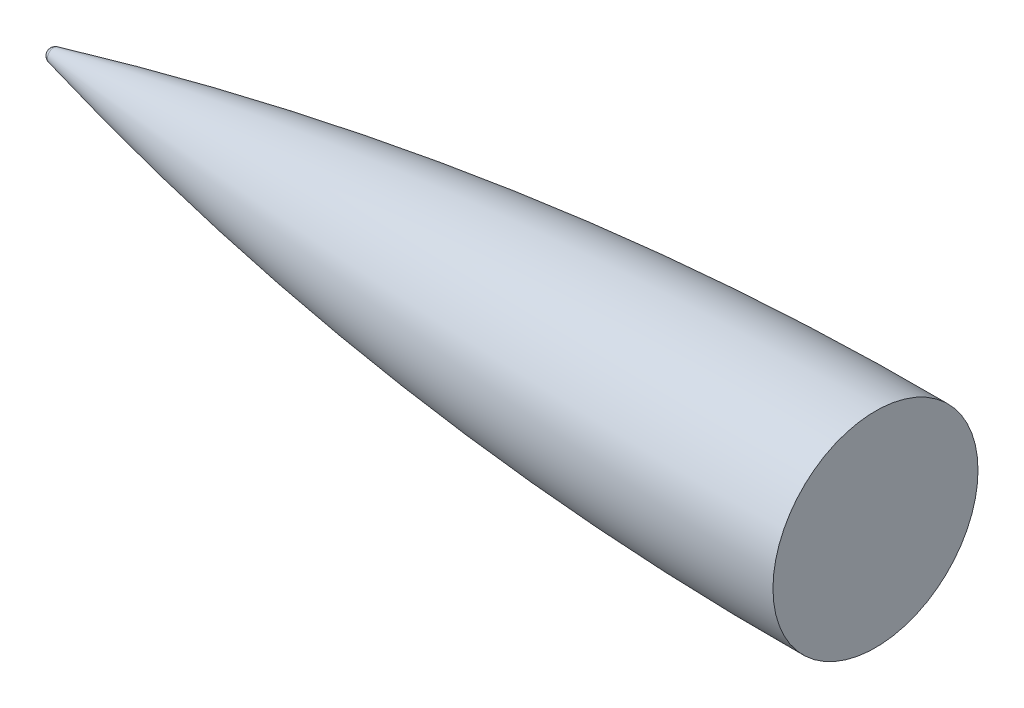
SolidWorks part; units mm, degrees
ref_plane "Front Plane" through (0, 0, 0) normal (0, 0, 1) x (1, 0, 0)
ref_plane "Top Plane" through (0, 0, 0) normal (0, 1, 0) x (1, 0, 0)
ref_plane "Right Plane" through (0, 0, 0) normal (1, 0, 0) x (0, 0, -1)
sketch "Sketch1" plane through (0, 0, 0) normal (0, 0, 1) x (1, 0, 0)
  line L0 (0, 0) -> (325.525, 0) construction
  line L1 (325.525, 0) -> (325.525, 39.37)
  line L2 (8.025, 0) -> (8.025, 30.9534) construction
  line L3 (325.525, 0) -> (8.025, 0)
  arc A1 (9.9641, 2.4679) -> (8.025, 0) centre (10.565, 0) ccw
  arc A2 (325.525, 39.37) -> (9.9641, 2.4679) centre (317.6933, -1261.3375) ccw
  arc A3 (13.105, 0) -> (9.9641, 2.4679) centre (10.565, 0) ccw construction
  arc A4 (8.025, 0) -> (13.105, 0) centre (10.565, 0) ccw construction
  arc A5 (8.025, 1.9942) -> (0, 0) centre (317.6933, -1261.3375) ccw construction
  arc A6 (9.9641, 2.4679) -> (8.025, 1.9942) centre (317.6933, -1261.3375) ccw construction
  point P4 (10.565, 0)
  point P5 (9.9641, 2.4679)
  point P11 (8.025, 0)
  dimension "D1" = 39.37
  dimension "D2" = 10.565
  dimension "D3" = 2.4679
  dimension "D4" = 9.9641
  dimension "D5" = 317.5
revolve "Revolve1" add sketch "Sketch1" angle 360 about L3
equation "\"r_n\"= 0.1'nose tip radius"
equation "\"R_nc\"= 3.1 / 2'nosecone base radius"
equation "\"L_nc\"= 12.5'exposed length of the nosecone"
equation "\"rho\"= ( \"R_nc\" ^ 2 + \"L_nc\" ^ 2 ) / ( 2 * \"R_nc\" )'ogive radius"
equation "\"x_0\"= \"L_nc\" - sqr ( ( \"rho\" - \"r_n\" ) ^ 2 - ( \"rho\" - \"R_nc\" ) ^ 2 )'center of tip sphere"
equation "\"y_t\"= \"r_n\" * ( \"rho\" - \"R_nc\" ) / ( \"rho\" - \"r_n\" )'y-coordinate of tangency point"
equation "\"x_t\"= \"x_0\" - sqr ( \"r_n\" ^ 2 - \"y_t\" ^ 2 )'x-coordinate of tangency point"
equation "\"x_a\"= \"x_0\" - \"r_n\"'apex point"
equation "\"D1@Sketch1\"=\"R_nc\""
equation "\"D2@Sketch1\"=\"x_0\""
equation "\"D3@Sketch1\"=\"y_t\""
equation "\"D4@Sketch1\"=\"x_t\""
equation "\"D5@Sketch1\"=\"L_nc\""
